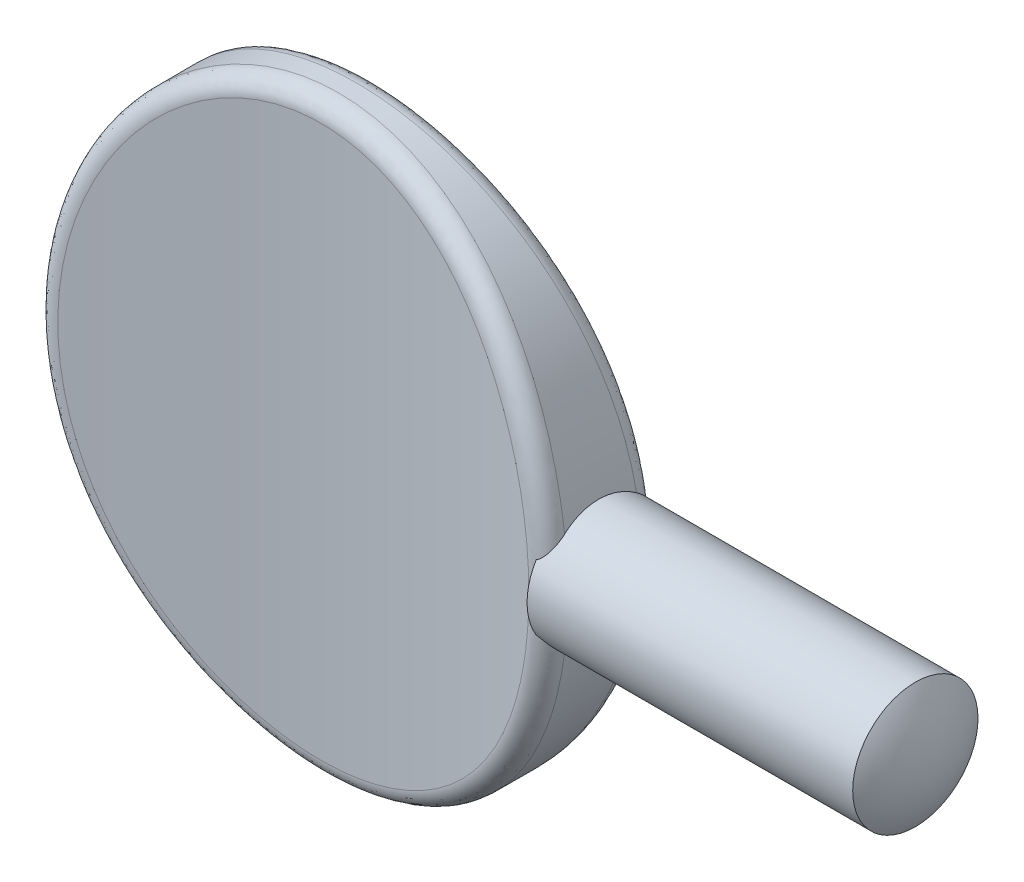
SolidWorks part; units mm, degrees
ref_plane "Front" through (0, 0, 0) normal (0, 0, 1) x (1, 0, 0)
ref_plane "Top" through (0, 0, 0) normal (0, 1, 0) x (1, 0, 0)
ref_plane "Right" through (0, 0, 0) normal (1, 0, 0) x (0, 0, -1)
ref_axis "Axis1" through (-50, 0, 0) along (1, 0, 0)
sketch "Sketch1" plane through (0, 0, 0) normal (0, 0, 1) x (1, 0, 0)
  line L0 (0, 0) -> (22.606, 0) construction
  line L1 (13.208, -2.413) -> (13.208, 2.413)
  line L2 (13.208, -2.413) -> (9.6776, -2.413) construction
  ellipse E0 centre (0, 0) end of major axis (0, -11.303) minor radius 9.906
  dimension "D2" = 3.302
  dimension "B" = 19.812
  dimension "L" = 12.7
extrude "Extrude1" add sketch "Sketch1" along normal mid plane 4.572
sketch "Sketch2" plane through (0, 0, 0) normal (0, 1, 0) x (1, 0, 0)
  line L0 (9.906, 2.286) -> (-9.906, 2.286) construction
  line L1 (0, 0) -> (0, 1.1721) construction
  line L2 (-1.7991, 0) -> (2.0444, 0) construction
  line L3 (-9.906, -2.286) -> (9.906, -2.286) construction
  line L6 (-9.906, 2.286) -> (-9.906, -2.286)
  line L7 (9.906, 2.286) -> (9.906, -2.286)
  arc A0 (-9.906, 2.286) -> (9.906, 2.286) centre (0, 40.2844) ccw
  arc A1 (-9.906, -2.286) -> (9.906, -2.286) centre (0, -40.2844) cw
extrude "Cut-Extrude1" cut sketch "Sketch2" against normal through all and the other way through all flip side to cut
fillet "Fillet3" radius 0.6773 2 edges at (-9.9037, -0.2444, 2.2854) (0.1692, 11.3014, -1.0164)
sketch "Sketch3" plane through (0, 0, 0) normal (0, 1, 0) x (1, 0, 0)
  line L0 (22.606, 0) -> (22.606, -2.4455) construction
  line L1 (0, 0) -> (21.0288, 0) construction
  line L2 (0, 0) -> (22.606, 0) construction
  line L3 (13.208, 2.413) -> (13.208, 0) construction
  line L4 (13.208, 2.413) -> (21.8792, 2.413)
  line L6 (13.208, 2.413) -> (9.3367, 2.413)
  line L7 (9.0722, 2.0783) -> (9.0722, 0)
  line L8 (9.3367, 0) -> (9.3367, 2.413) construction
  line L9 (9.0722, 0) -> (22.606, 0)
  arc A0 (9.3367, 2.413) -> (9.0722, 2.0783) centre (8.9927, 2.413) cw
  arc A1 (22.606, 0) -> (21.8792, 2.413) centre (18.2372, 0) ccw
  arc A3 (-9.906, 2.286) -> (9.906, 2.286) centre (0, 40.2844) ccw construction
revolve "Revolve1" add sketch "Sketch3" angle 360 about L0
cosmetic thread "Cosmetic Thread1" [suppressed]
sketch "Sketch4" plane through (0, 0, 0) normal (0, 0, 1) x (1, 0, 0)
  line L0 (0, 0) -> (27.7993, 0) construction
  line L1 (21.6958, 2.413) -> (21.8792, 2.0955)
  line L2 (21.8792, 2.0955) -> (22.0625, 2.413)
  line L3 (22.0625, 2.413) -> (22.0625, 2.7796)
  line L4 (22.0625, 2.7796) -> (21.6958, 2.7796)
  line L5 (21.6958, 2.7796) -> (21.6958, 2.413)
  line L6 (21.8792, 2.413) -> (21.8792, -2.413) construction
  dimension "D1" = 4.191
  dimension "D2" = 4.826
revolve "Cut-Revolve10" [suppressed] cut sketch "Sketch4" angle 360 about L0
pattern_linear "LPattern10" [suppressed] count 24 along (-1, 0, 0) of bodies 109
equation "\"D2@Sketch1\" = \"B@Sketch1\" / 6"
equation "\"D1@Fillet3\" = \"C1@Sketch2\" / 3"
equation "\"DIA@Sketch3\" = \"D@Sketch1\""
equation "\"D1@Sketch4\" = \"D2@Cosmetic Thread1\""
equation "\"D2@Sketch4\" = \"DIA@Sketch3\""
equation "\"D1@LPattern10\" = \"L@Sketch1\" / \"P@LPattern10\" - 1"
